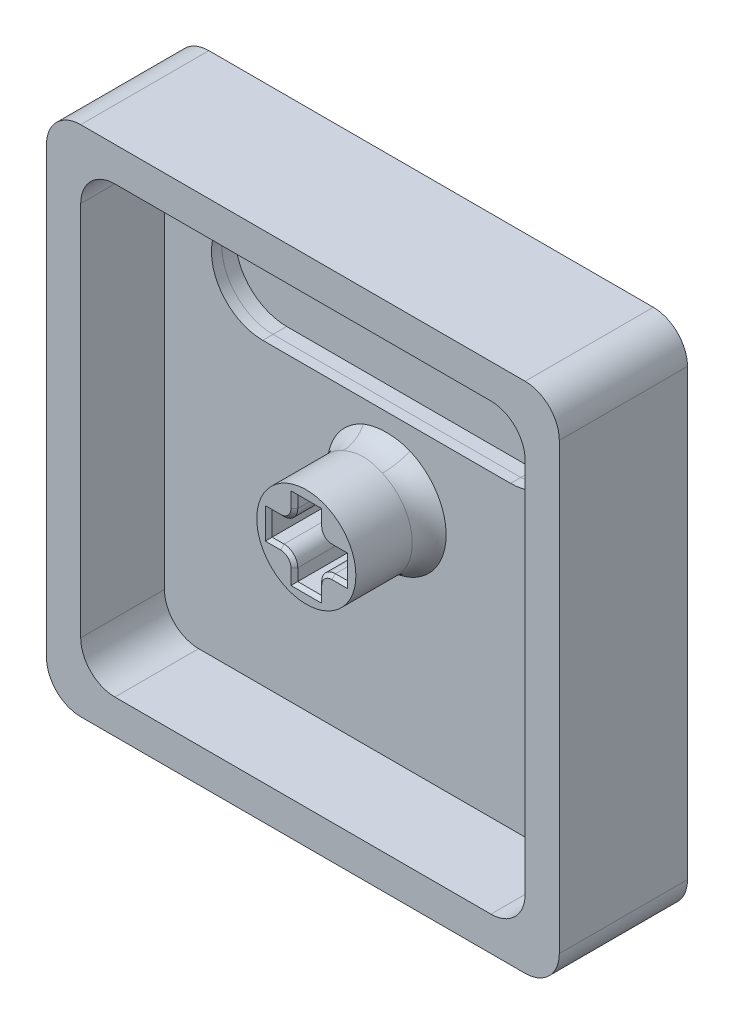
SolidWorks part; units mm, degrees
note: The reader was unsure of these and kept them because the rebuilt part matched: shared geometry of "草图1<6>", "草图1<7>".
other "标注1"
sketch "草图2" plane through (15, -15, 10) normal (0.3933, -0.7926, 0.466) x (0.9059, 0.4207, -0.0491)
ref_plane "前视基准面" through (0, 0, 0) normal (0, 0, 1) x (1, 0, 0)
ref_plane "上视基准面" through (0, 0, 0) normal (0, 1, 0) x (1, 0, 0)
ref_plane "右视基准面" through (0, 0, 0) normal (1, 0, 0) x (0, 0, -1)
sketch "草图1" plane through (0, 0, 0) normal (0, 0, 1) x (1, 0, 0)
  line L0 (-13, 15) -> (13, 15)
  line L1 (-11, 13) -> (11, 13)
  line L2 (-13, 11) -> (-13, -11)
  line L3 (-11, -13) -> (11, -13)
  line L4 (13, 11) -> (13, -11)
  line L5 (0, -13) -> (0, 13) construction
  line L6 (-13, 0) -> (13, 0) construction
  line L7 (15, 13) -> (15, -13)
  line L8 (-13, -15) -> (13, -15)
  line L9 (-15, 13) -> (-15, -13)
  line L10 (-13, -13) -> (13, -13) construction
  line L11 (-2.2, 0.7) -> (2.2, 0.7)
  line L12 (-2.2, 0.7) -> (-2.2, -0.7)
  line L13 (-2.2, -0.7) -> (2.2, -0.7)
  line L14 (2.2, 0.7) -> (2.2, -0.7)
  line L15 (0, -0.7) -> (0, 0.7) construction
  line L16 (-2.2, 0) -> (2.2, 0) construction
  line L17 (-0.7, 2.2) -> (0.7, 2.2)
  line L18 (-0.7, 2.2) -> (-0.7, -2.2)
  line L19 (-0.7, -2.2) -> (0.7, -2.2)
  line L20 (0.7, 2.2) -> (0.7, -2.2)
  line L21 (0, -2.2) -> (0, 2.2) construction
  line L22 (-0.7, 0) -> (0.7, 0) construction
  line L23 (13, 13) -> (13, -13) construction
  line L24 (-13, 13) -> (13, 13) construction
  line L25 (-13, 13) -> (-13, -13) construction
  line L26 (-15, 15) -> (-15, -15) construction
  line L27 (-15, -15) -> (15, -15) construction
  line L28 (15, 15) -> (15, -15) construction
  line L29 (-15, 15) -> (15, 15) construction
  line L36 (-13, 0) -> (-2.5, 0) construction
  circle A0 centre (0, 0) radius 2.9
  arc A1 (11, -13) -> (13, -11) centre (11, -11) ccw
  arc A2 (13, 11) -> (11, 13) centre (11, 11) ccw
  arc A3 (-13, 11) -> (-11, 13) centre (-11, 11) cw
  arc A4 (-13, -11) -> (-11, -13) centre (-11, -11) ccw
  arc A5 (-15, -13) -> (-13, -15) centre (-13, -13) ccw
  arc A6 (13, -15) -> (15, -13) centre (13, -13) ccw
  arc A7 (15, 13) -> (13, 15) centre (13, 13) ccw
  arc A8 (-15, 13) -> (-13, 15) centre (-13, 13) cw
  point P0 (0, 0)
  point P19 (13, -13)
  point P66 (0.0162, 0.0162)
  dimension "D4" = 5.8
  dimension "D9" = 2
  dimension "D1" = 30
  dimension "D2" = 30
  dimension "D5" = 4.4
  dimension "D6" = 1.4
  dimension "D7" = 4.4
  dimension "D8" = 1.4
  dimension "D3" = 2
extrude "凸台-拉伸1" add sketch "草图1" along normal blind 5.5 contours A8 L9 A5 L8 A6 L7 A7 L0 A4 L2 A3 L1 A2 L4 A1 L3
extrude "凸台-拉伸2" add sketch "草图1<6>" along normal blind 5.3 separate body contours A0 L17 L20 L11 L14 L13 L19 L18 L12
sketch "草图1<6>" plane through (0, 0, 0) normal (0, 0, 1) x (1, 0, 0) same geometry as "草图1"
extrude "凸台-拉伸3" add sketch "草图1<7>" against normal blind 2 contours L8 A6 L7 A7 L0 A8 L9 A5
sketch "草图1<7>" plane through (0, 0, 0) normal (0, 0, 1) x (1, 0, 0) same geometry as "草图1"
sketch "草图3" plane through (0, 0, 0) normal (0, 0, 1) x (1, 0, 0)
  line L8 (0.7, 0.7) -> (0.7, 2.2)
  line L10 (0.7, 0.7) -> (0.7, 2.2)
  line L15 (-0.7, 0.7) -> (-2.2, 0.7)
  line L16 (-2.2, 0.7) -> (-2.2, -0.7)
  line L17 (-2.2, -0.7) -> (-0.7, -0.7)
  line L19 (0.7, 2.2) -> (-0.7, 2.2)
  line L20 (0.7, 2.2) -> (-0.7, 2.2)
  line L21 (0.7, -0.7) -> (2.2, -0.7)
  line L22 (2.2, -0.7) -> (2.2, 0.7)
  line L23 (2.2, 0.7) -> (0.7, 0.7)
  line L27 (-0.7, 0.7) -> (-2.2, 0.7)
  line L28 (-2.2, 0.7) -> (-2.2, -0.7)
  line L29 (-2.2, -0.7) -> (-0.7, -0.7)
  line L33 (0.7, -0.7) -> (2.2, -0.7)
  line L34 (2.2, -0.7) -> (2.2, 0.7)
  line L35 (2.2, 0.7) -> (0.7, 0.7)
  line L36 (-0.7, 2.2) -> (-0.7, 0.7)
  line L37 (-0.7, 2.2) -> (-0.7, 0.7)
  line L38 (-0.7, -0.7) -> (-0.7, -2.2)
  line L39 (-0.7, -0.7) -> (-0.7, -2.2)
  line L40 (-0.7, -2.2) -> (0.7, -2.2)
  line L41 (-0.7, -2.2) -> (0.7, -2.2)
  line L42 (0.7, -2.2) -> (0.7, -0.7)
  line L43 (0.7, -2.2) -> (0.7, -0.7)
  dimension "D1" = 0
extrude "凸台-拉伸4" add sketch "草图3" along normal blind 2
sketch "草图5" plane through (0, 0, 0) normal (0, 0, 1) x (1, 0, 0)
  line L6 (7.25, 7.5) -> (-7.25, 7.5) construction
  line L7 (7.25, 4.5) -> (-7.25, 4.5)
  line L9 (7.25, 10.5) -> (-7.25, 10.5)
  line L10 (0, 0) -> (0, -50000) construction
  arc A0 (7.25, 4.5) -> (7.25, 10.5) centre (7.25, 7.5) ccw
  arc A1 (-7.25, 10.5) -> (-7.25, 4.5) centre (-7.25, 7.5) ccw
  point P2 (0, 7.5)
  dimension "D2" = 3
  dimension "D1" = 14.5
  dimension "D3" = 7.5
extrude "切除-拉伸1" cut sketch "草图5" against normal up to next
sketch "草图6" plane through (0, 0, -2) normal (0, 0, -1) x (-1, 0, 0)
  line L10 (7.25, 4.5) -> (-7.25, 4.5) construction
  line L11 (-7.25, 10.5) -> (7.25, 10.5) construction
  line L12 (7.25, 4.5) -> (-7.25, 4.5)
  line L13 (-7.25, 10.5) -> (7.25, 10.5)
  arc A0 (7.25, 4.5) -> (7.25, 10.5) centre (7.25, 7.5) ccw construction
  arc A1 (-7.25, 10.5) -> (-7.25, 4.5) centre (-7.25, 7.5) ccw construction
  arc A2 (7.25, 4.5) -> (7.25, 10.5) centre (7.25, 7.5) ccw
  arc A3 (-7.25, 10.5) -> (-7.25, 4.5) centre (-7.25, 7.5) ccw
extrude "凸台-拉伸6" add sketch "草图6" against normal blind 1.2 separate body
sketch "草图7" plane through (0, 0, 0) normal (0, 0, 1) x (1, 0, 0)
  line L0 (7.25, 4.5) -> (-7.25, 4.5) construction
  line L1 (7.25, 10.5) -> (-7.25, 10.5) construction
  line L2 (7.25, 4.5) -> (-7.25, 4.5)
  line L3 (7.25, 10.5) -> (-7.25, 10.5)
  line L4 (-13, 11) -> (-13, -11)
  line L5 (-11, -13) -> (11, -13)
  line L6 (13, -11) -> (13, 11)
  line L7 (11, 13) -> (-11, 13)
  line L8 (-13, 11) -> (-13, -11)
  line L9 (-11, -13) -> (11, -13)
  line L10 (13, -11) -> (13, 11)
  line L11 (11, 13) -> (-11, 13)
  circle A0 centre (0, 0) radius 2.9 construction
  circle A1 centre (0, 0) radius 2.9
  arc A2 (7.25, 4.5) -> (7.25, 10.5) centre (7.25, 7.5) ccw construction
  arc A3 (-7.25, 10.5) -> (-7.25, 4.5) centre (-7.25, 7.5) ccw construction
  arc A4 (-13, -11) -> (-11, -13) centre (-11, -11) ccw
  arc A5 (11, -13) -> (13, -11) centre (11, -11) ccw
  arc A6 (13, 11) -> (11, 13) centre (11, 11) ccw
  arc A7 (-11, 13) -> (-13, 11) centre (-11, 11) ccw
  arc A8 (-13, -11) -> (-11, -13) centre (-11, -11) ccw
  arc A9 (11, -13) -> (13, -11) centre (11, -11) ccw
  arc A10 (13, 11) -> (11, 13) centre (11, 11) ccw
  arc A11 (-11, 13) -> (-13, 11) centre (-11, 11) ccw
  arc A12 (7.25, 4.5) -> (7.25, 10.5) centre (7.25, 7.5) ccw
  arc A13 (-7.25, 10.5) -> (-7.25, 4.5) centre (-7.25, 7.5) ccw
  dimension "D1" = 0
extrude "凸台-拉伸7" add sketch "草图7" along normal blind 0.6 separate body
fillet "圆角4" radius 0.8 4 edges at (-0.7, 0.7, 3.65) (0.7, 0.7, 3.65) (-0.7, -0.7, 3.65) (0.7, -0.7, 3.65)
chamfer "倒角1" distance 0.2 angle 45 16 edges at (-0.7, 1.85, 5.3) (-1.85, 0.7, 5.3) (-1.85, -0.7, 5.3) (-0.7, -1.85, 5.3) (0, -2.2, 5.3) (0.7, -1.85, 5.3) (1.85, -0.7, 5.3) (1.85, 0.7, 5.3) (0.7, 1.85, 5.3) (0, 2.2, 5.3) (-0.9343, -0.9343, 5.3) (0.9343, -0.9343, 5.3) (0.9343, 0.9343, 5.3) (-0.9343, 0.9343, 5.3) (-2.2, 0, 5.3) (2.2, 0, 5.3)
fillet "圆角5" radius 2 1 edges at (2.9, 0, 0)
